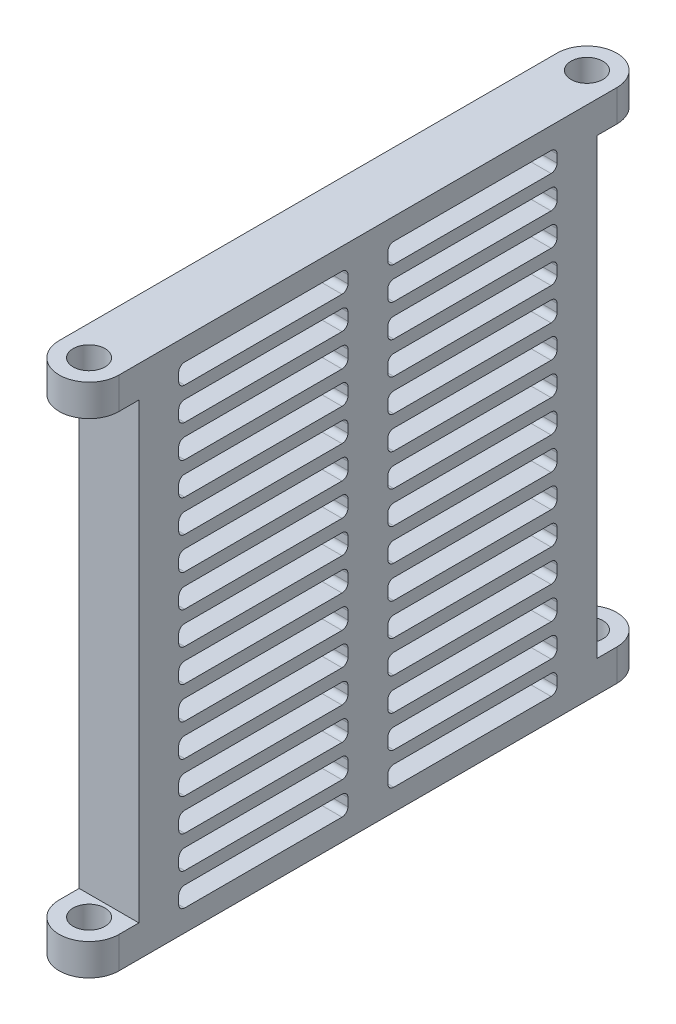
SolidWorks part; units mm, degrees
ref_plane "Front Plane" through (0, 0, 0) normal (0, 0, 1) x (1, 0, 0)
ref_plane "Top Plane" through (0, 0, 0) normal (0, 1, 0) x (1, 0, 0)
ref_plane "Right Plane" through (0, 0, 0) normal (1, 0, 0) x (0, 0, -1)
sketch "Sketch2" plane through (0, 0, 0) normal (0, 1, 0) x (1, 0, 0)
  line L0 (-3, 0) -> (-3, -50)
  line L1 (3, -50) -> (3, 0)
  arc A0 (3, 0) -> (-3, 0) centre (0, 0) ccw
  arc A1 (-3, -50) -> (3, -50) centre (0, -50) ccw
  circle A2 centre (0, 0) radius 1.6
  circle A3 centre (0, -50) radius 1.6
  dimension "D1" = 3.2
  dimension "D2" = 3
  dimension "D3" = 50
extrude "Boss-Extrude1" add sketch "Sketch2" along normal blind 3.175
sketch "Sketch3" plane through (0, 3.175, 0) normal (0, 1, 0) x (1, 0, 0)
  line L0 (-3, 0) -> (-3, -50) construction
  line L1 (-3, -2) -> (3, -2)
  line L2 (-3, -2) -> (-3, -48)
  line L3 (-3, -48) -> (3, -48)
  line L4 (3, -2) -> (3, -48)
  line L5 (3, -50) -> (3, 0) construction
  circle A0 centre (0, -50) radius 1.6 construction
  point P9 (0, -48)
  dimension "D1" = 2
  dimension "D2" = 2
extrude "Boss-Extrude2" add sketch "Sketch3" along normal blind 45.48
ref_plane "Plane1" through (0, 25.915, 0) normal (0, 1, 0) x (1, 0, 0)
mirror "Mirror2" about plane through (0, 25.915, 0) normal (0, 1, 0) of "Boss-Extrude1"
sketch "Sketch4" plane through (3, 0, 0) normal (1, 0, 0) x (0, 0, -1)
  line L0 (-2, 48.655) -> (-48, 48.655) construction
  line L1 (-6.6, 7.4236) -> (-22.4, 7.4236)
  line L2 (-6, 6.8236) -> (-6, 6.0236)
  line L3 (-2, 3.175) -> (-48, 3.175) construction
  line L4 (-6.6, 5.4236) -> (-22.4, 5.4236)
  line L5 (-23, 6.8236) -> (-23, 6.0236)
  line L11 (-25, 51.83) -> (-25, 0) construction
  line L12 (-50, 51.83) -> (0, 51.83) construction
  line L24 (-50, 0) -> (0, 0) construction
  line L25 (-2, 48.655) -> (-2, 3.175) construction
  line L30 (-6.6, 49.655) -> (-22.4, 49.655)
  line L39 (-6, 49.055) -> (-6, 48.255)
  line L40 (-6.6, 47.655) -> (-22.4, 47.655)
  line L41 (-23, 49.055) -> (-23, 48.255)
  line L46 (-6, 49.655) -> (-23, 47.655) construction
  line L47 (-6, 47.655) -> (-23, 49.655) construction
  line L64 (-6.6, 46.4064) -> (-22.4, 46.4064)
  line L69 (-6, 45.8064) -> (-6, 45.0064)
  line L70 (-6.6, 44.4064) -> (-22.4, 44.4064)
  line L71 (-23, 45.8064) -> (-23, 45.0064)
  line L72 (-2, 45.4064) -> (-48, 45.4064) construction
  line L73 (-6, 46.4064) -> (-23, 44.4064) construction
  line L74 (-6, 44.4064) -> (-23, 46.4064) construction
  line L75 (-6.6, 43.1579) -> (-22.4, 43.1579)
  line L76 (-6, 42.5579) -> (-6, 41.7579)
  line L77 (-6.6, 41.1579) -> (-22.4, 41.1579)
  line L78 (-23, 42.5579) -> (-23, 41.7579)
  line L79 (-2, 42.1579) -> (-48, 42.1579) construction
  line L132 (-6, 43.1579) -> (-23, 41.1579) construction
  line L133 (-6, 41.1579) -> (-23, 43.1579) construction
  line L134 (-6.6, 39.9093) -> (-22.4, 39.9093)
  line L135 (-6, 39.3093) -> (-6, 38.5093)
  line L136 (-6.6, 37.9093) -> (-22.4, 37.9093)
  line L137 (-23, 39.3093) -> (-23, 38.5093)
  line L138 (-2, 38.9093) -> (-48, 38.9093) construction
  line L139 (-6, 39.9093) -> (-23, 37.9093) construction
  line L140 (-6, 37.9093) -> (-23, 39.9093) construction
  line L141 (-6.6, 36.6607) -> (-22.4, 36.6607)
  line L142 (-6, 36.0607) -> (-6, 35.2607)
  line L143 (-6.6, 34.6607) -> (-22.4, 34.6607)
  line L144 (-23, 36.0607) -> (-23, 35.2607)
  line L145 (-2, 35.6607) -> (-48, 35.6607) construction
  line L146 (-6, 36.6607) -> (-23, 34.6607) construction
  line L147 (-6, 34.6607) -> (-23, 36.6607) construction
  line L148 (-6.6, 33.4121) -> (-22.4, 33.4121)
  line L149 (-6, 32.8121) -> (-6, 32.0121)
  line L186 (-2, 6.4236) -> (-48, 6.4236) construction
  line L187 (-6, 7.4236) -> (-23, 5.4236) construction
  line L188 (-6, 5.4236) -> (-23, 7.4236) construction
  line L189 (-6.6, 4.175) -> (-22.4, 4.175)
  line L190 (-6, 3.575) -> (-6, 2.775)
  line L191 (-6.6, 2.175) -> (-22.4, 2.175)
  line L192 (-23, 3.575) -> (-23, 2.775)
  line L193 (-2, 3.175) -> (-48, 3.175) construction
  line L194 (-6, 4.175) -> (-23, 2.175) construction
  line L195 (-6, 2.175) -> (-23, 4.175) construction
  line L196 (-44, 8.6721) -> (-27, 10.6721) construction
  line L197 (-44, 10.6721) -> (-27, 8.6721) construction
  line L198 (-44, 11.9207) -> (-27, 13.9207) construction
  line L199 (-44, 13.9207) -> (-27, 11.9207) construction
  line L200 (-44, 15.1693) -> (-27, 17.1693) construction
  line L201 (-6.6, 31.4121) -> (-22.4, 31.4121)
  line L202 (-23, 32.8121) -> (-23, 32.0121)
  line L203 (-2, 32.4121) -> (-48, 32.4121) construction
  line L204 (-6, 33.4121) -> (-23, 31.4121) construction
  line L205 (-6, 31.4121) -> (-23, 33.4121) construction
  line L206 (-6.6, 30.1636) -> (-22.4, 30.1636)
  line L207 (-6, 29.5636) -> (-6, 28.7636)
  line L208 (-6.6, 28.1636) -> (-22.4, 28.1636)
  line L209 (-23, 29.5636) -> (-23, 28.7636)
  line L210 (-2, 29.1636) -> (-48, 29.1636) construction
  line L211 (-6, 30.1636) -> (-23, 28.1636) construction
  line L212 (-6, 28.1636) -> (-23, 30.1636) construction
  line L213 (-6.6, 26.915) -> (-22.4, 26.915)
  line L214 (-6, 26.315) -> (-6, 25.515)
  line L215 (-6.6, 24.915) -> (-22.4, 24.915)
  line L216 (-23, 26.315) -> (-23, 25.515)
  line L217 (-2, 25.915) -> (-48, 25.915) construction
  line L218 (-6, 26.915) -> (-23, 24.915) construction
  line L219 (-6, 24.915) -> (-23, 26.915) construction
  line L220 (-6.6, 23.6664) -> (-22.4, 23.6664)
  line L221 (-6, 23.0664) -> (-6, 22.2664)
  line L222 (-6.6, 21.6664) -> (-22.4, 21.6664)
  line L223 (-23, 23.0664) -> (-23, 22.2664)
  line L224 (-2, 22.6664) -> (-48, 22.6664) construction
  line L225 (-6, 23.6664) -> (-23, 21.6664) construction
  line L226 (-6, 21.6664) -> (-23, 23.6664) construction
  line L227 (-6.6, 20.4179) -> (-22.4, 20.4179)
  line L228 (-6, 19.8179) -> (-6, 19.0179)
  line L229 (-6.6, 18.4179) -> (-22.4, 18.4179)
  line L230 (-23, 19.8179) -> (-23, 19.0179)
  line L231 (-2, 19.4179) -> (-48, 19.4179) construction
  line L232 (-6, 20.4179) -> (-23, 18.4179) construction
  line L233 (-6, 18.4179) -> (-23, 20.4179) construction
  line L234 (-6.6, 17.1693) -> (-22.4, 17.1693)
  line L235 (-6, 16.5693) -> (-6, 15.7693)
  line L236 (-6.6, 15.1693) -> (-22.4, 15.1693)
  line L237 (-23, 16.5693) -> (-23, 15.7693)
  line L238 (-2, 16.1693) -> (-48, 16.1693) construction
  line L239 (-6, 17.1693) -> (-23, 15.1693) construction
  line L240 (-6, 15.1693) -> (-23, 17.1693) construction
  line L241 (-6.6, 13.9207) -> (-22.4, 13.9207)
  line L242 (-6, 13.3207) -> (-6, 12.5207)
  line L243 (-6.6, 11.9207) -> (-22.4, 11.9207)
  line L244 (-23, 13.3207) -> (-23, 12.5207)
  line L245 (-2, 12.9207) -> (-48, 12.9207) construction
  line L246 (-6, 13.9207) -> (-23, 11.9207) construction
  line L247 (-6, 11.9207) -> (-23, 13.9207) construction
  line L248 (-6.6, 10.6721) -> (-22.4, 10.6721)
  line L249 (-6, 10.0721) -> (-6, 9.2721)
  line L250 (-6.6, 8.6721) -> (-22.4, 8.6721)
  line L251 (-23, 10.0721) -> (-23, 9.2721)
  line L252 (-2, 9.6721) -> (-48, 9.6721) construction
  line L253 (-6, 10.6721) -> (-23, 8.6721) construction
  line L254 (-6, 8.6721) -> (-23, 10.6721) construction
  line L255 (-44, 17.1693) -> (-27, 15.1693) construction
  line L256 (-44, 18.4179) -> (-27, 20.4179) construction
  line L257 (-44, 20.4179) -> (-27, 18.4179) construction
  line L258 (-44, 21.6664) -> (-27, 23.6664) construction
  line L259 (-44, 23.6664) -> (-27, 21.6664) construction
  line L260 (-44, 24.915) -> (-27, 26.915) construction
  line L261 (-44, 26.915) -> (-27, 24.915) construction
  line L262 (-44, 28.1636) -> (-27, 30.1636) construction
  line L263 (-44, 30.1636) -> (-27, 28.1636) construction
  line L264 (-44, 31.4121) -> (-27, 33.4121) construction
  line L265 (-44, 33.4121) -> (-27, 31.4121) construction
  line L266 (-44, 2.175) -> (-27, 4.175) construction
  line L267 (-44, 4.175) -> (-27, 2.175) construction
  line L268 (-44, 5.4236) -> (-27, 7.4236) construction
  line L269 (-44, 7.4236) -> (-27, 5.4236) construction
  line L270 (-44, 34.6607) -> (-27, 36.6607) construction
  line L271 (-44, 36.6607) -> (-27, 34.6607) construction
  line L272 (-44, 37.9093) -> (-27, 39.9093) construction
  line L273 (-44, 39.9093) -> (-27, 37.9093) construction
  line L274 (-44, 41.1579) -> (-27, 43.1579) construction
  line L275 (-44, 43.1579) -> (-27, 41.1579) construction
  line L276 (-44, 44.4064) -> (-27, 46.4064) construction
  line L277 (-44, 46.4064) -> (-27, 44.4064) construction
  line L278 (-44, 47.655) -> (-27, 49.655) construction
  line L279 (-44, 49.655) -> (-27, 47.655) construction
  line L280 (-27, 10.0721) -> (-27, 9.2721)
  line L333 (-43.4, 8.6721) -> (-27.6, 8.6721)
  line L334 (-44, 10.0721) -> (-44, 9.2721)
  line L335 (-43.4, 10.6721) -> (-27.6, 10.6721)
  line L336 (-27, 13.3207) -> (-27, 12.5207)
  line L337 (-43.4, 11.9207) -> (-27.6, 11.9207)
  line L338 (-44, 13.3207) -> (-44, 12.5207)
  line L339 (-43.4, 13.9207) -> (-27.6, 13.9207)
  line L340 (-27, 16.5693) -> (-27, 15.7693)
  line L341 (-43.4, 15.1693) -> (-27.6, 15.1693)
  line L342 (-44, 16.5693) -> (-44, 15.7693)
  line L343 (-43.4, 17.1693) -> (-27.6, 17.1693)
  line L344 (-27, 19.8179) -> (-27, 19.0179)
  line L345 (-43.4, 18.4179) -> (-27.6, 18.4179)
  line L346 (-44, 19.8179) -> (-44, 19.0179)
  line L347 (-43.4, 20.4179) -> (-27.6, 20.4179)
  line L348 (-27, 23.0664) -> (-27, 22.2664)
  line L349 (-43.4, 21.6664) -> (-27.6, 21.6664)
  line L350 (-44, 23.0664) -> (-44, 22.2664)
  line L351 (-43.4, 23.6664) -> (-27.6, 23.6664)
  line L352 (-27, 26.315) -> (-27, 25.515)
  line L353 (-43.4, 24.915) -> (-27.6, 24.915)
  line L354 (-44, 26.315) -> (-44, 25.515)
  line L355 (-43.4, 26.915) -> (-27.6, 26.915)
  line L356 (-27, 29.5636) -> (-27, 28.7636)
  line L357 (-43.4, 28.1636) -> (-27.6, 28.1636)
  line L358 (-44, 29.5636) -> (-44, 28.7636)
  line L359 (-43.4, 30.1636) -> (-27.6, 30.1636)
  line L360 (-27, 32.8121) -> (-27, 32.0121)
  line L361 (-43.4, 31.4121) -> (-27.6, 31.4121)
  line L362 (-27, 3.575) -> (-27, 2.775)
  line L363 (-43.4, 2.175) -> (-27.6, 2.175)
  line L364 (-44, 3.575) -> (-44, 2.775)
  line L365 (-43.4, 4.175) -> (-27.6, 4.175)
  line L366 (-44, 32.8121) -> (-44, 32.0121)
  line L367 (-43.4, 33.4121) -> (-27.6, 33.4121)
  line L368 (-27, 36.0607) -> (-27, 35.2607)
  line L369 (-43.4, 34.6607) -> (-27.6, 34.6607)
  line L370 (-44, 36.0607) -> (-44, 35.2607)
  line L371 (-43.4, 36.6607) -> (-27.6, 36.6607)
  line L372 (-27, 39.3093) -> (-27, 38.5093)
  line L373 (-43.4, 37.9093) -> (-27.6, 37.9093)
  line L374 (-44, 39.3093) -> (-44, 38.5093)
  line L375 (-43.4, 39.9093) -> (-27.6, 39.9093)
  line L376 (-27, 42.5579) -> (-27, 41.7579)
  line L377 (-43.4, 41.1579) -> (-27.6, 41.1579)
  line L378 (-44, 42.5579) -> (-44, 41.7579)
  line L379 (-43.4, 43.1579) -> (-27.6, 43.1579)
  line L380 (-27, 45.8064) -> (-27, 45.0064)
  line L381 (-43.4, 44.4064) -> (-27.6, 44.4064)
  line L382 (-44, 45.8064) -> (-44, 45.0064)
  line L383 (-43.4, 46.4064) -> (-27.6, 46.4064)
  line L384 (-27, 49.055) -> (-27, 48.255)
  line L385 (-43.4, 47.655) -> (-27.6, 47.655)
  line L386 (-44, 49.055) -> (-44, 48.255)
  line L387 (-43.4, 49.655) -> (-27.6, 49.655)
  line L388 (-27, 6.8236) -> (-27, 6.0236)
  line L389 (-43.4, 5.4236) -> (-27.6, 5.4236)
  line L390 (-44, 6.8236) -> (-44, 6.0236)
  line L391 (-43.4, 7.4236) -> (-27.6, 7.4236)
  arc A72 (-22.4, 7.4236) -> (-23, 6.8236) centre (-22.4, 6.8236) ccw
  arc A73 (-22.4, 5.4236) -> (-23, 6.0236) centre (-22.4, 6.0236) cw
  arc A74 (-6.6, 7.4236) -> (-6, 6.8236) centre (-6.6, 6.8236) cw
  arc A75 (-6, 6.0236) -> (-6.6, 5.4236) centre (-6.6, 6.0236) cw
  arc A76 (-22.4, 49.655) -> (-23, 49.055) centre (-22.4, 49.055) ccw
  arc A77 (-22.4, 47.655) -> (-23, 48.255) centre (-22.4, 48.255) cw
  arc A78 (-6.6, 49.655) -> (-6, 49.055) centre (-6.6, 49.055) cw
  arc A79 (-6, 48.255) -> (-6.6, 47.655) centre (-6.6, 48.255) cw
  arc A80 (-22.4, 46.4064) -> (-23, 45.8064) centre (-22.4, 45.8064) ccw
  arc A81 (-22.4, 44.4064) -> (-23, 45.0064) centre (-22.4, 45.0064) cw
  arc A82 (-6.6, 46.4064) -> (-6, 45.8064) centre (-6.6, 45.8064) cw
  arc A83 (-6, 45.0064) -> (-6.6, 44.4064) centre (-6.6, 45.0064) cw
  arc A84 (-22.4, 43.1579) -> (-23, 42.5579) centre (-22.4, 42.5579) ccw
  arc A85 (-22.4, 41.1579) -> (-23, 41.7579) centre (-22.4, 41.7579) cw
  arc A86 (-6.6, 43.1579) -> (-6, 42.5579) centre (-6.6, 42.5579) cw
  arc A87 (-6, 41.7579) -> (-6.6, 41.1579) centre (-6.6, 41.7579) cw
  arc A88 (-22.4, 39.9093) -> (-23, 39.3093) centre (-22.4, 39.3093) ccw
  arc A89 (-22.4, 37.9093) -> (-23, 38.5093) centre (-22.4, 38.5093) cw
  arc A90 (-6.6, 39.9093) -> (-6, 39.3093) centre (-6.6, 39.3093) cw
  arc A91 (-6, 38.5093) -> (-6.6, 37.9093) centre (-6.6, 38.5093) cw
  arc A92 (-22.4, 36.6607) -> (-23, 36.0607) centre (-22.4, 36.0607) ccw
  arc A93 (-22.4, 34.6607) -> (-23, 35.2607) centre (-22.4, 35.2607) cw
  arc A94 (-6.6, 36.6607) -> (-6, 36.0607) centre (-6.6, 36.0607) cw
  arc A95 (-6, 35.2607) -> (-6.6, 34.6607) centre (-6.6, 35.2607) cw
  arc A96 (-22.4, 33.4121) -> (-23, 32.8121) centre (-22.4, 32.8121) ccw
  arc A97 (-22.4, 31.4121) -> (-23, 32.0121) centre (-22.4, 32.0121) cw
  arc A98 (-6.6, 33.4121) -> (-6, 32.8121) centre (-6.6, 32.8121) cw
  arc A99 (-6, 32.0121) -> (-6.6, 31.4121) centre (-6.6, 32.0121) cw
  arc A100 (-22.4, 30.1636) -> (-23, 29.5636) centre (-22.4, 29.5636) ccw
  arc A101 (-22.4, 28.1636) -> (-23, 28.7636) centre (-22.4, 28.7636) cw
  arc A102 (-6.6, 30.1636) -> (-6, 29.5636) centre (-6.6, 29.5636) cw
  arc A103 (-6, 28.7636) -> (-6.6, 28.1636) centre (-6.6, 28.7636) cw
  arc A104 (-22.4, 26.915) -> (-23, 26.315) centre (-22.4, 26.315) ccw
  arc A105 (-22.4, 24.915) -> (-23, 25.515) centre (-22.4, 25.515) cw
  arc A106 (-6.6, 26.915) -> (-6, 26.315) centre (-6.6, 26.315) cw
  arc A107 (-6, 25.515) -> (-6.6, 24.915) centre (-6.6, 25.515) cw
  arc A108 (-22.4, 23.6664) -> (-23, 23.0664) centre (-22.4, 23.0664) ccw
  arc A109 (-22.4, 21.6664) -> (-23, 22.2664) centre (-22.4, 22.2664) cw
  arc A110 (-6.6, 23.6664) -> (-6, 23.0664) centre (-6.6, 23.0664) cw
  arc A111 (-6, 22.2664) -> (-6.6, 21.6664) centre (-6.6, 22.2664) cw
  arc A112 (-22.4, 20.4179) -> (-23, 19.8179) centre (-22.4, 19.8179) ccw
  arc A113 (-22.4, 18.4179) -> (-23, 19.0179) centre (-22.4, 19.0179) cw
  arc A114 (-6.6, 20.4179) -> (-6, 19.8179) centre (-6.6, 19.8179) cw
  arc A115 (-6, 19.0179) -> (-6.6, 18.4179) centre (-6.6, 19.0179) cw
  arc A116 (-22.4, 17.1693) -> (-23, 16.5693) centre (-22.4, 16.5693) ccw
  arc A117 (-22.4, 15.1693) -> (-23, 15.7693) centre (-22.4, 15.7693) cw
  arc A118 (-6.6, 17.1693) -> (-6, 16.5693) centre (-6.6, 16.5693) cw
  arc A119 (-6, 15.7693) -> (-6.6, 15.1693) centre (-6.6, 15.7693) cw
  arc A120 (-22.4, 13.9207) -> (-23, 13.3207) centre (-22.4, 13.3207) ccw
  arc A121 (-22.4, 11.9207) -> (-23, 12.5207) centre (-22.4, 12.5207) cw
  arc A122 (-6.6, 13.9207) -> (-6, 13.3207) centre (-6.6, 13.3207) cw
  arc A123 (-6, 12.5207) -> (-6.6, 11.9207) centre (-6.6, 12.5207) cw
  arc A124 (-22.4, 10.6721) -> (-23, 10.0721) centre (-22.4, 10.0721) ccw
  arc A125 (-22.4, 8.6721) -> (-23, 9.2721) centre (-22.4, 9.2721) cw
  arc A126 (-6.6, 10.6721) -> (-6, 10.0721) centre (-6.6, 10.0721) cw
  arc A127 (-6, 9.2721) -> (-6.6, 8.6721) centre (-6.6, 9.2721) cw
  arc A180 (-22.4, 4.175) -> (-23, 3.575) centre (-22.4, 3.575) ccw
  arc A181 (-22.4, 2.175) -> (-23, 2.775) centre (-22.4, 2.775) cw
  arc A182 (-6.6, 4.175) -> (-6, 3.575) centre (-6.6, 3.575) cw
  arc A183 (-6, 2.775) -> (-6.6, 2.175) centre (-6.6, 2.775) cw
  arc A184 (-44, 2.775) -> (-43.4, 2.175) centre (-43.4, 2.775) ccw
  arc A185 (-43.4, 4.175) -> (-44, 3.575) centre (-43.4, 3.575) ccw
  arc A186 (-27.6, 2.175) -> (-27, 2.775) centre (-27.6, 2.775) ccw
  arc A187 (-27.6, 4.175) -> (-27, 3.575) centre (-27.6, 3.575) cw
  arc A188 (-44, 9.2721) -> (-43.4, 8.6721) centre (-43.4, 9.2721) ccw
  arc A189 (-43.4, 10.6721) -> (-44, 10.0721) centre (-43.4, 10.0721) ccw
  arc A190 (-27.6, 8.6721) -> (-27, 9.2721) centre (-27.6, 9.2721) ccw
  arc A191 (-27.6, 10.6721) -> (-27, 10.0721) centre (-27.6, 10.0721) cw
  arc A192 (-44, 12.5207) -> (-43.4, 11.9207) centre (-43.4, 12.5207) ccw
  arc A193 (-43.4, 13.9207) -> (-44, 13.3207) centre (-43.4, 13.3207) ccw
  arc A194 (-27.6, 11.9207) -> (-27, 12.5207) centre (-27.6, 12.5207) ccw
  arc A195 (-27.6, 13.9207) -> (-27, 13.3207) centre (-27.6, 13.3207) cw
  arc A196 (-44, 15.7693) -> (-43.4, 15.1693) centre (-43.4, 15.7693) ccw
  arc A197 (-43.4, 17.1693) -> (-44, 16.5693) centre (-43.4, 16.5693) ccw
  arc A198 (-27.6, 15.1693) -> (-27, 15.7693) centre (-27.6, 15.7693) ccw
  arc A199 (-27.6, 17.1693) -> (-27, 16.5693) centre (-27.6, 16.5693) cw
  arc A200 (-44, 19.0179) -> (-43.4, 18.4179) centre (-43.4, 19.0179) ccw
  arc A201 (-43.4, 20.4179) -> (-44, 19.8179) centre (-43.4, 19.8179) ccw
  arc A202 (-27.6, 18.4179) -> (-27, 19.0179) centre (-27.6, 19.0179) ccw
  arc A203 (-27.6, 20.4179) -> (-27, 19.8179) centre (-27.6, 19.8179) cw
  arc A204 (-44, 22.2664) -> (-43.4, 21.6664) centre (-43.4, 22.2664) ccw
  arc A205 (-43.4, 23.6664) -> (-44, 23.0664) centre (-43.4, 23.0664) ccw
  arc A206 (-27.6, 21.6664) -> (-27, 22.2664) centre (-27.6, 22.2664) ccw
  arc A207 (-27.6, 23.6664) -> (-27, 23.0664) centre (-27.6, 23.0664) cw
  arc A208 (-44, 25.515) -> (-43.4, 24.915) centre (-43.4, 25.515) ccw
  arc A209 (-43.4, 26.915) -> (-44, 26.315) centre (-43.4, 26.315) ccw
  arc A210 (-27.6, 24.915) -> (-27, 25.515) centre (-27.6, 25.515) ccw
  arc A211 (-27.6, 26.915) -> (-27, 26.315) centre (-27.6, 26.315) cw
  arc A212 (-44, 28.7636) -> (-43.4, 28.1636) centre (-43.4, 28.7636) ccw
  arc A213 (-43.4, 30.1636) -> (-44, 29.5636) centre (-43.4, 29.5636) ccw
  arc A214 (-27.6, 28.1636) -> (-27, 28.7636) centre (-27.6, 28.7636) ccw
  arc A215 (-27.6, 30.1636) -> (-27, 29.5636) centre (-27.6, 29.5636) cw
  arc A216 (-44, 32.0121) -> (-43.4, 31.4121) centre (-43.4, 32.0121) ccw
  arc A217 (-43.4, 33.4121) -> (-44, 32.8121) centre (-43.4, 32.8121) ccw
  arc A218 (-27.6, 31.4121) -> (-27, 32.0121) centre (-27.6, 32.0121) ccw
  arc A219 (-27.6, 33.4121) -> (-27, 32.8121) centre (-27.6, 32.8121) cw
  arc A220 (-44, 35.2607) -> (-43.4, 34.6607) centre (-43.4, 35.2607) ccw
  arc A221 (-43.4, 36.6607) -> (-44, 36.0607) centre (-43.4, 36.0607) ccw
  arc A222 (-27.6, 34.6607) -> (-27, 35.2607) centre (-27.6, 35.2607) ccw
  arc A223 (-27.6, 36.6607) -> (-27, 36.0607) centre (-27.6, 36.0607) cw
  arc A224 (-44, 38.5093) -> (-43.4, 37.9093) centre (-43.4, 38.5093) ccw
  arc A225 (-43.4, 39.9093) -> (-44, 39.3093) centre (-43.4, 39.3093) ccw
  arc A226 (-27.6, 37.9093) -> (-27, 38.5093) centre (-27.6, 38.5093) ccw
  arc A227 (-27.6, 39.9093) -> (-27, 39.3093) centre (-27.6, 39.3093) cw
  arc A228 (-44, 41.7579) -> (-43.4, 41.1579) centre (-43.4, 41.7579) ccw
  arc A229 (-43.4, 43.1579) -> (-44, 42.5579) centre (-43.4, 42.5579) ccw
  arc A230 (-27.6, 41.1579) -> (-27, 41.7579) centre (-27.6, 41.7579) ccw
  arc A231 (-27.6, 43.1579) -> (-27, 42.5579) centre (-27.6, 42.5579) cw
  arc A232 (-44, 45.0064) -> (-43.4, 44.4064) centre (-43.4, 45.0064) ccw
  arc A233 (-43.4, 46.4064) -> (-44, 45.8064) centre (-43.4, 45.8064) ccw
  arc A234 (-27.6, 44.4064) -> (-27, 45.0064) centre (-27.6, 45.0064) ccw
  arc A235 (-27.6, 46.4064) -> (-27, 45.8064) centre (-27.6, 45.8064) cw
  arc A236 (-44, 48.255) -> (-43.4, 47.655) centre (-43.4, 48.255) ccw
  arc A237 (-43.4, 49.655) -> (-44, 49.055) centre (-43.4, 49.055) ccw
  arc A238 (-27.6, 47.655) -> (-27, 48.255) centre (-27.6, 48.255) ccw
  arc A239 (-27.6, 49.655) -> (-27, 49.055) centre (-27.6, 49.055) cw
  arc A240 (-44, 6.0236) -> (-43.4, 5.4236) centre (-43.4, 6.0236) ccw
  arc A241 (-43.4, 7.4236) -> (-44, 6.8236) centre (-43.4, 6.8236) ccw
  arc A242 (-27.6, 5.4236) -> (-27, 6.0236) centre (-27.6, 6.0236) ccw
  arc A243 (-27.6, 7.4236) -> (-27, 6.8236) centre (-27.6, 6.8236) cw
  point P10 (-14.5, 48.655)
  point P13 (-14.25, 34.325)
  point P14 (-14.25, 31.825)
  point P15 (-14.25, 29.325)
  point P16 (-14.25, 26.825)
  point P36 (-14.5, 45.4064)
  point P55 (-14.5, 42.1579)
  point P74 (-14.5, 38.9093)
  point P93 (-14.5, 35.6607)
  point P112 (-14.5, 32.4121)
  point P131 (-14.5, 29.1636)
  point P150 (-14.5, 25.915)
  point P169 (-14.5, 22.6664)
  point P188 (-14.5, 19.4179)
  point P207 (-14.5, 16.1693)
  point P226 (-14.5, 12.9207)
  point P245 (-14.5, 9.6721)
  point P328 (-14.5, 6.4236)
  point P347 (-14.5, 3.175)
  point P543 (-35.5, 3.175)
  point P544 (-35.5, 6.4236)
  point P545 (-35.5, 9.6721)
  point P546 (-35.5, 12.9207)
  point P547 (-35.5, 16.1693)
  point P548 (-35.5, 19.4179)
  point P549 (-35.5, 22.6664)
  point P550 (-35.5, 25.915)
  point P551 (-35.5, 29.1636)
  point P552 (-35.5, 32.4121)
  point P553 (-35.5, 35.6607)
  point P554 (-35.5, 38.9093)
  point P555 (-35.5, 42.1579)
  point P556 (-35.5, 45.4064)
  point P557 (-35.5, 48.655)
  dimension "D6" = 1.2486
  dimension "D4" = 0.6
  dimension "D1" = 2
  dimension "D2" = 4
  dimension "D3" = 2
  dimension "D5" = 15
extrude "Cut-Extrude1" cut sketch "Sketch4" against normal through all
equation "\"D2@Sketch3\"=\"D1@Sketch3\""
